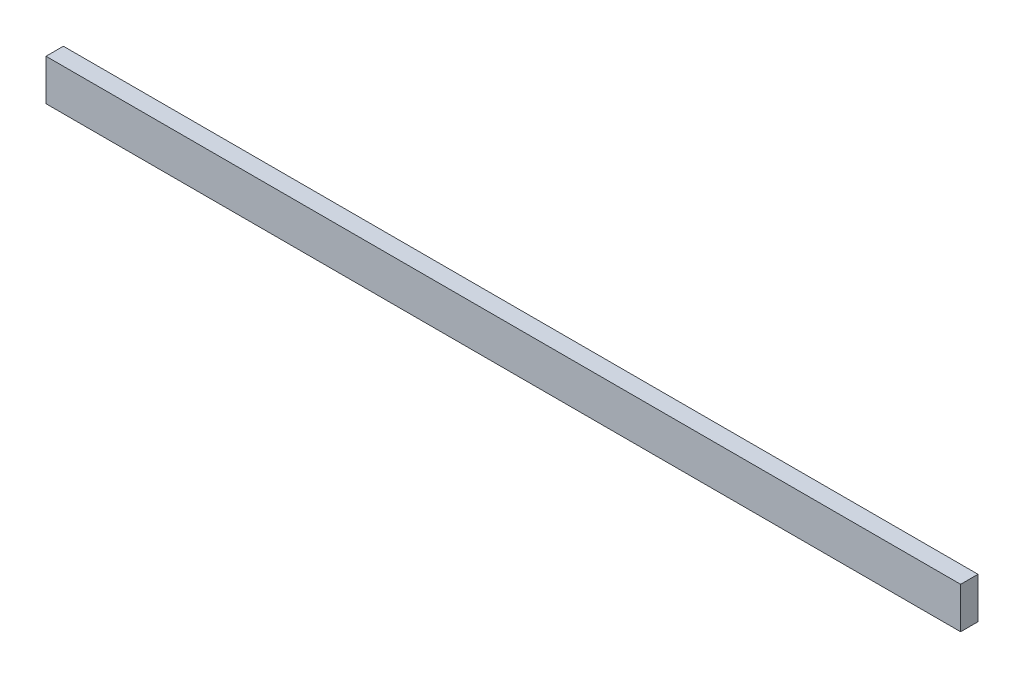
SolidWorks part; units mm, degrees
ref_plane "Front" through (0, 0, 0) normal (0, 0, 1) x (1, 0, 0)
ref_plane "Top" through (0, 0, 0) normal (0, 1, 0) x (1, 0, 0)
ref_plane "Right" through (0, 0, 0) normal (1, 0, 0) x (0, 0, -1)
sketch "Sketch1" plane through (0, 0, 0) normal (0, 1, 0) x (1, 0, 0)
  line L5 (1000.5, 9.75) -> (1000.5, -9.75) construction
  line L6 (1000.5, 9.5) -> (0, 9.5)
  line L7 (1000.5, 9.5) -> (1000.5, -9.5)
  line L8 (1000.5, -9.5) -> (0, -9.5)
  line L9 (0, 9.5) -> (0, -9.5)
  line L10 (1000.5, 9.5) -> (0, -9.5) construction
  line L11 (1000.5, -9.5) -> (0, 9.5) construction
  point P0 (500.25, 0)
  dimension "D1" = 19
extrude "Boss-Extrude1" add sketch "Sketch1" along normal blind 45
